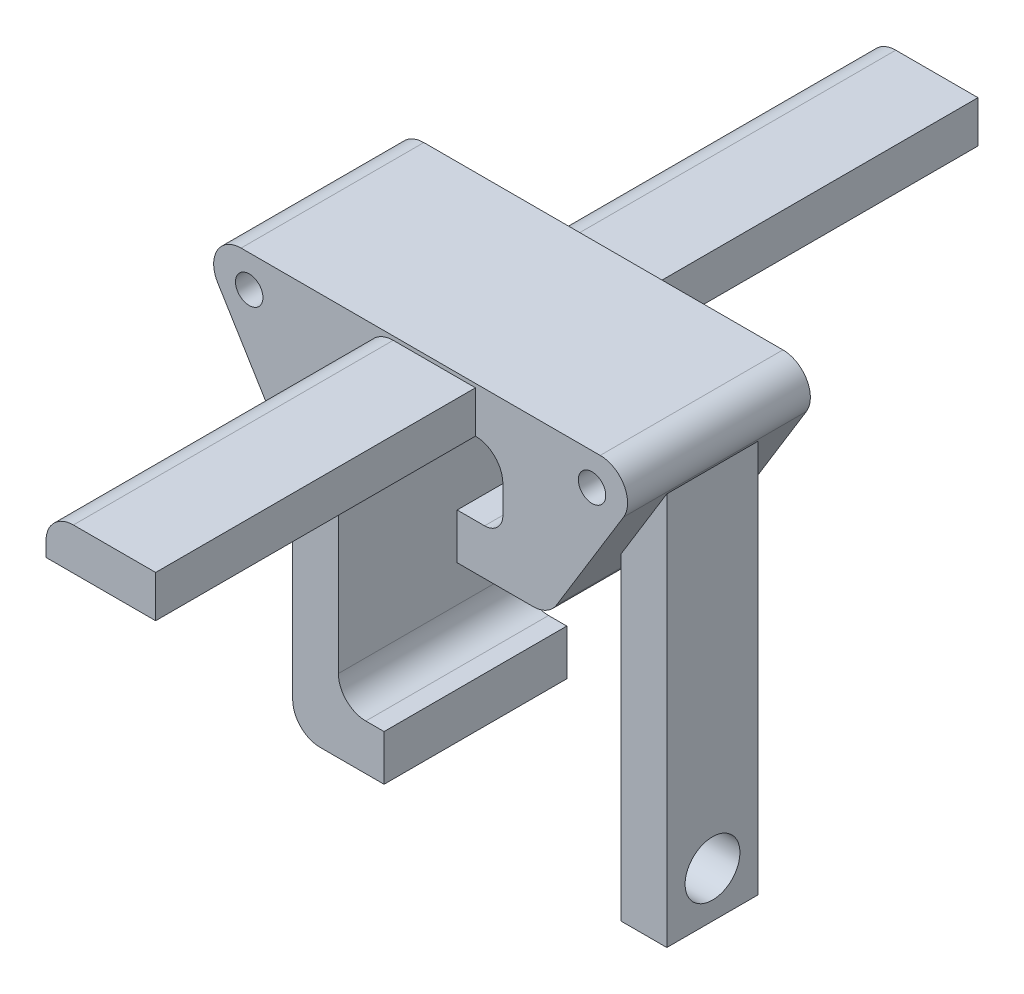
SolidWorks part; units mm, degrees
ref_plane "Front Plane" through (0, 0, 0) normal (0, 0, 1) x (1, 0, 0)
ref_plane "Top Plane" through (0, 0, 0) normal (0, 1, 0) x (1, 0, 0)
ref_plane "Right Plane" through (0, 0, 0) normal (1, 0, 0) x (0, 0, -1)
sketch "Sketch2" plane through (0, 0, 0) normal (0, 0, 1) x (1, 0, 0)
  line L0 (0, 0) -> (0, -8)
  line L1 (0, -8) -> (-5, -8)
  line L2 (0, 0) -> (-18, 0)
  line L3 (-18, 0) -> (-18, -33)
  line L4 (-18, -33) -> (-13, -33)
  dimension "D1" = 8
  dimension "D2" = 5
  dimension "D3" = 8
  dimension "D4" = 25
  dimension "D5" = 18
extrude "Extrude-Thin1" add sketch "Sketch2" along normal blind 20 thin thin type one direction wall 5
sketch "Sketch3" plane through (0, 0, 20) normal (0, 0, 1) x (1, 0, 0)
  line L0 (5, 5) -> (16, 5)
  line L1 (16, 5) -> (5, -13)
  line L2 (5, -13) -> (5, 5)
  line L3 (-23, 5) -> (-34, 5)
  line L4 (-34, 5) -> (-23, -13)
  line L5 (-23, 5) -> (-23, -38) construction
  line L6 (-23, -13) -> (-23, 5)
  dimension "D1" = 50
extrude "Boss-Extrude1" add sketch "Sketch3" against normal up to surface (20 mm away) up to face at (-9, -14.5, 0)
fillet "Fillet1" radius 3 6 edges at (-18, -33, 10) (-23, -38, 10) (-23, -13, 10) (5, -13, 10) (16, 5, 10) (-34, 5, 10)
sketch "Sketch4" plane through (0, 0, 20) normal (0, 0, 1) x (1, 0, 0)
  line L0 (-27.7593, 1.5) -> (-30.7458, -0.3251) construction
  line L1 (-31.2107, 0.4356) -> (-23.4402, -12.2797) construction
  line L2 (-27.7593, 1.5) -> (-27.7593, 5) construction
  line L3 (10.6508, 5) -> (-28.6508, 5) construction
  line L4 (9.7593, 1.5) -> (9.7593, 5) construction
  line L5 (9.7593, 1.5) -> (12.7458, -0.3251) construction
  line L6 (5.8773, -11.5644) -> (13.2107, 0.4356) construction
  circle A0 centre (9.7593, 1.5) radius 1.5
  circle A1 centre (-27.7593, 1.5) radius 1.5
  point P14 (9.7593, 3)
  point P15 (11.0392, 0.7178)
  point P16 (-29.0392, 0.7178)
  point P19 (-27.7593, 3)
  dimension "D1" = 3
  dimension "D2" = 2
  dimension "D3" = 2
  dimension "D4" = 2
  dimension "D5" = 2
extrude "Cut-Extrude1" cut sketch "Sketch4" against normal up to surface (20 mm away) up to face at (-10.747, -14.5192, 0)
fillet "Fillet2" radius 3 2 edges at (0, 0, 10) (-18, 0, 10)
fillet "Fillet3" radius 2 1 edges at (0, -8, 10)
sketch "Sketch5" plane through (0, 0, 20) normal (0, 0, 1) x (1, 0, 0)
  line L0 (-26.0604, -1.56) -> (-13.452, 5.44) construction
  line L1 (-3, 0) -> (-15, 0)
  line L2 (-3, 0) -> (-3, 4.5805)
  line L3 (-3, 4.5805) -> (-15, 4.5805)
  line L4 (-15, 0) -> (-15, 4.5805)
extrude "Boss-Extrude2" add sketch "Sketch5" along normal blind 35
extrude "Boss-Extrude3" add sketch "Sketch5<2>" along direction (0, 0, -1) on the side against the normal blind 35 from surface starting at face at (8.2593, 1.5, 0)
sketch "Sketch5<2>" plane through (0, 0, 20) normal (0, 0, 1) x (1, 0, 0) same geometry as "Sketch5"
fillet "Fillet4" radius 3 2 edges at (-15, 4.5805, -17.5) (-15, 4.5805, 37.5)
sketch "Sketch6" plane through (0, 0, 20) normal (0, 0, 1) x (1, 0, 0)
  line L1 (7.9444, 0) -> (12.9444, 0)
  line L2 (7.9444, 0) -> (7.9444, -43)
  line L3 (7.9444, -43) -> (12.9444, -43)
  line L4 (12.9444, 0) -> (12.9444, -43)
  line L5 (-20, -38) -> (-13, -38) construction
  line L6 (5.8773, -11.5644) -> (13.2107, 0.4356) construction
  circle A0 centre (9.7593, 1.5) radius 1.5 construction
  dimension "D1" = 5
  dimension "D2" = 5
extrude "Boss-Extrude4" add sketch "Sketch6" against normal offset from surface (10 mm away) 5 from offset 5 up to face at (-10.176, -11.0269, 0) offset against normal yes
sketch "Sketch7" plane through (12.9444, 0, 0) normal (1, 0, 0) x (0, 0, -1)
  line L0 (-5, -43) -> (-15, -43) construction
  line L1 (-5, -43) -> (-5, 0) construction
  line L2 (-15, -43) -> (-15, 0) construction
  circle A0 centre (-10, -38) radius 3
  circle A1 centre (-10, -38) radius 5 construction
  dimension "D1" = 6
extrude "Cut-Extrude2" cut sketch "Sketch7" against normal up to surface (5 mm away) up to face at (7.9444, -25.5909, 10)
